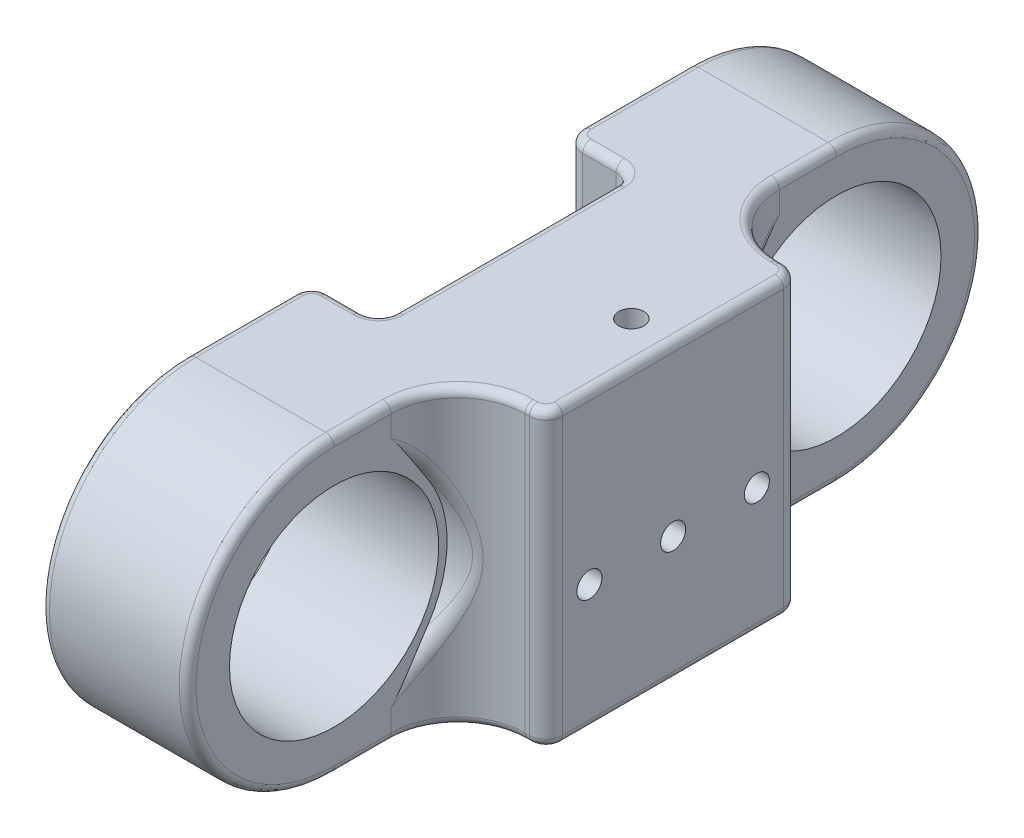
SolidWorks part; units mm, degrees
ref_plane "Front Plane" through (0, 0, 0) normal (0, 0, 1) x (1, 0, 0)
ref_plane "Top Plane" through (0, 0, 0) normal (0, 1, 0) x (1, 0, 0)
ref_plane "Right Plane" through (0, 0, 0) normal (1, 0, 0) x (0, 0, -1)
sketch "Sketch2" plane through (0, 0, 0) normal (0, 1, 0) x (1, 0, 0)
  line L0 (-11.1125, 19.29) -> (-0.9525, 19.29)
  line L1 (11.1125, -60.325) -> (-11.1125, -60.325)
  line L2 (11.1125, -60.325) -> (11.1125, 60.325)
  line L3 (11.1125, 60.325) -> (-11.1125, 60.325)
  line L4 (-11.1125, -60.325) -> (-11.1125, 60.325)
  line L5 (11.1125, -60.325) -> (-11.1125, 60.325) construction
  line L6 (11.1125, 60.325) -> (-11.1125, -60.325) construction
  line L7 (-0.9525, 19.29) -> (-0.9525, -19.29)
  line L8 (-0.9525, -19.29) -> (-11.1125, -19.29)
  line L9 (-11.1125, 18.02) -> (-0.9525, 18.02) construction
  line L10 (-182.965, -60.325) -> (-182.965, 60.325) construction
  line L12 (11.1125, 19.29) -> (24.4475, 19.29)
  line L13 (11.1125, 19.29) -> (11.1125, -19.29)
  line L14 (11.1125, -19.29) -> (24.4475, -19.29)
  line L15 (24.4475, 19.29) -> (24.4475, -19.29)
  line L16 (-0.9525, 18.02) -> (-0.9525, -18.02) construction
  line L17 (-0.9525, -18.02) -> (-11.1125, -18.02) construction
  line L18 (-11.1125, -18.02) -> (-0.9525, -18.02) construction
  line L19 (24.4475, 0) -> (-0.9525, 0) construction
  line L22 (-131.3125, 18.02) -> (-131.3125, -18.02) construction
  line L23 (-375.0525, 0) -> (31.3475, 0) construction
  circle A1 centre (18.0975, 0) radius 1.905
  point P0 (0, 0)
  point P9 (-0.9525, 0)
  point P21 (-6.0325, 18.02)
  point P22 (0, 0)
  dimension "D6" = 3.81
  dimension "D1" = 22.225
  dimension "D2" = 10.16
  dimension "D3" = 25.4
  dimension "D4" = 1.27
  dimension "D5" = 1.27
  dimension "D7" = 6.35
extrude "Boss-Extrude2" add sketch "Sketch2" along normal mid plane 44.45 contours L7 L8 L4 L1 L2 L3 L0 | L13 L12 L15 L14 | A1 region at (1.0328, 0, 0)
fillet "Fillet1" radius 10.16 2 edges at (11.1125, 0, 19.29) (11.1125, 0, -19.29)
sketch "Sketch3" plane through (11.1125, 0, 0) normal (1, 0, 0) x (0, 0, -1)
  line L0 (-60.325, 22.225) -> (-29.45, 22.225) construction
  line L1 (-60.325, -22.225) -> (-29.45, -22.225) construction
  line L2 (-60.325, 22.225) -> (-60.325, -22.225) construction
  line L3 (0, 19.558) -> (0, -19.558) construction
  line L4 (60.325, -22.225) -> (29.45, -22.225)
  line L5 (60.325, 22.225) -> (60.325, -22.225)
  line L6 (29.45, 22.225) -> (60.325, 22.225)
  line L7 (-29.45, -22.225) -> (-29.45, 22.225)
  line L8 (-29.45, 22.225) -> (-60.325, 22.225)
  line L9 (-60.325, 22.225) -> (-60.325, -22.225)
  line L10 (-60.325, -22.225) -> (-29.45, -22.225)
  line L12 (-29.45, 22.225) -> (-60.325, 22.225)
  line L13 (-60.325, 22.225) -> (-60.325, -22.225)
  line L14 (-60.325, -22.225) -> (-29.45, -22.225)
  line L15 (29.45, -22.225) -> (29.45, 22.225)
  line L20 (-29.45, -22.225) -> (-29.45, 22.225)
  circle A0 centre (-38.1, 0) radius 15.875
  circle A1 centre (-38.1, 0) radius 15.875 construction
  arc A2 (-38.1, 22.225) -> (-38.1, -22.225) centre (-38.1, 0) ccw
  arc A3 (38.1, 22.225) -> (38.1, -22.225) centre (38.1, 0) cw
  circle A4 centre (38.1, 0) radius 15.875
  circle A5 centre (-38.1, 0) radius 17.145
  circle A6 centre (38.1, 0) radius 17.145
  line M3 (-60.325, 22.225) -> (-60.325, -22.225)
  line M4 (-60.325, -22.225) -> (-29.45, -22.225)
  dimension "D1" = 0
  dimension "D2" = 34.29
extrude "Cut-Extrude1" cut sketch "Sketch3" against normal up to surface and the other way up to surface contours A0 | A2 L12 M3 | A2 L13 M4 | A4 | L6 A3 L5 | L5 A3 L4 | A0 | A4 region at (11.1125, -17.2606, -55.3606) region at (11.1125, 17.2606, -55.3606) region at (11.1125, 0, -40.4962) region at (11.1125, -17.2606, 55.3606) region at (11.1125, 0, 40.4962) region at (11.1125, 17.2606, 55.3606) up to face at (-11.1125, 0, 39.8075) other way up to face at (24.4475, 0, 0)
extrude "Cut-Extrude2" cut sketch "Sketch3<3>" along normal up to surface (13.335 mm away) contours A6 | A5 up to face at (24.4475, 0, 0)
sketch "Sketch3<3>" plane through (11.1125, 0, 0) normal (1, 0, 0) x (0, 0, -1) same geometry as "Sketch3"
fillet "Fillet2" radius 2.54 2 edges at (15.6715, 0.7919, 20.9733) (15.6715, 0.7919, -20.9733)
fillet "Fillet3" radius 2.54 6 edges at (-0.9525, 0, -19.29) (-0.9525, 0, 19.29) (-11.1125, 0, 19.29) (-11.1125, 0, -19.29) (24.4475, 0, 19.29) (24.4475, 0, -19.29)
fillet "Fillet4" radius 1.27 38 edges at (-11.1125, 22.225, 29.965) (-10.3686, 22.225, 20.0339) (-6.0325, 22.225, 19.29) (-1.6964, 22.225, 18.5461) (-0.9525, 22.225, 0) (-1.6964, 22.225, -18.5461) (-6.0325, 22.225, -19.29) (-10.3686, 22.225, -20.0339) (-11.1125, 22.225, -29.965) (-11.1125, 0, -60.325) (-11.1125, -22.225, -29.965) (-10.3686, -22.225, -20.0339) (-6.0325, -22.225, -19.29) (-1.6964, -22.225, -18.5461) (-0.9525, -22.225, 0) (-1.6964, -22.225, 18.5461) (-6.0325, -22.225, 19.29) (-10.3686, -22.225, 20.0339) (-11.1125, -22.225, 29.965) (11.1125, -22.225, -33.775) (14.0883, -22.225, 22.2658) (24.4475, -22.225, 0) (14.0883, -22.225, -22.2658) (11.1125, 0, -60.325) (11.1125, 22.225, -33.775) (14.0883, 22.225, -22.2658) (24.4475, 22.225, 0) (14.0883, 22.225, 22.2658) (-11.1125, 0, 60.325) (11.1125, 0, 60.325) (21.59, -22.225, 19.29) (21.59, 22.225, 19.29) (23.7036, -22.225, 18.5461) (23.7036, -22.225, -18.5461) (21.59, -22.225, -19.29) (21.59, 22.225, -19.29) (23.7036, 22.225, -18.5461) (23.7036, 22.225, 18.5461)
sketch "Sketch4" plane through (0, -22.225, 0) normal (0, -1, 0) x (1, 0, 0)
  line L0 (24.4475, 19.29) -> (24.4475, -19.29) construction
  line L1 (3.81, 15.875) -> (13.335, 15.875) construction
  line L2 (3.81, 15.875) -> (3.81, 9.525) construction
  line L3 (3.81, 9.525) -> (13.335, 9.525) construction
  line L4 (13.335, 15.875) -> (13.335, 9.525) construction
  line L5 (3.81, 3.175) -> (13.335, 3.175) construction
  line L6 (3.81, 3.175) -> (3.81, -3.175) construction
  line L7 (3.81, -3.175) -> (13.335, -3.175) construction
  line L8 (13.335, 3.175) -> (13.335, -3.175) construction
  line L9 (3.81, -9.525) -> (13.335, -9.525) construction
  line L10 (3.81, -9.525) -> (3.81, -15.875) construction
  line L11 (3.81, -15.875) -> (13.335, -15.875) construction
  line L12 (13.335, -9.525) -> (13.335, -15.875) construction
  line L13 (24.4475, 0) -> (-0.9525, 0) construction
  line L14 (-0.9525, -16.75) -> (-0.9525, 16.75) construction
  line L15 (3.556, 16.129) -> (13.589, 16.129)
  line L16 (13.589, 16.129) -> (13.589, 9.271)
  line L17 (3.556, 9.271) -> (13.589, 9.271)
  line L18 (3.556, 16.129) -> (3.556, 9.271)
  line L19 (3.556, 3.429) -> (13.589, 3.429)
  line L20 (13.589, 3.429) -> (13.589, -3.429)
  line L21 (3.556, -3.429) -> (13.589, -3.429)
  line L22 (3.556, 3.429) -> (3.556, -3.429)
  line L23 (3.556, -9.271) -> (13.589, -9.271)
  line L24 (13.589, -9.271) -> (13.589, -16.129)
  line L25 (3.556, -16.129) -> (13.589, -16.129)
  line L26 (3.556, -9.271) -> (3.556, -16.129)
  point P12 (24.4475, 0)
  point P13 (13.335, 0)
  point P21 (8.5725, 15.875)
  dimension "D1" = 6.35
  dimension "D2" = 15.875
  dimension "D3" = 15.875
  dimension "D4" = 9.525
  dimension "D5" = 4.7625
  dimension "D6" = 0.254
extrude "Cut-Extrude3" cut sketch "Sketch4" against normal blind 25.4
sketch "Sketch5" plane through (-0.9525, 0, 0) normal (-1, 0, 0) x (0, 0, 1)
  line L0 (9.271, -22.225) -> (16.129, -22.225) construction
  line L1 (16.129, -22.225) -> (16.129, 3.175) construction
  line L2 (16.129, 3.175) -> (9.271, 3.175) construction
  line L3 (9.271, 3.175) -> (9.271, -22.225) construction
  line L4 (-3.429, -22.225) -> (3.429, -22.225) construction
  line L5 (3.429, -22.225) -> (3.429, 3.175) construction
  line L6 (3.429, 3.175) -> (-3.429, 3.175) construction
  line L7 (-3.429, 3.175) -> (-3.429, -22.225) construction
  line L8 (-16.129, -22.225) -> (-9.271, -22.225) construction
  line L9 (-9.271, -22.225) -> (-9.271, 3.175) construction
  line L10 (-9.271, 3.175) -> (-16.129, 3.175) construction
  line L11 (-16.129, 3.175) -> (-16.129, -22.225) construction
  line L12 (9.271, -22.225) -> (16.129, -22.225) construction
  line L13 (16.129, -22.225) -> (16.129, 3.175) construction
  line L14 (16.129, 3.175) -> (9.271, 3.175) construction
  line L15 (9.271, 3.175) -> (9.271, -22.225) construction
  line L16 (-3.429, -22.225) -> (3.429, -22.225) construction
  line L17 (3.429, -22.225) -> (3.429, 3.175) construction
  line L18 (3.429, 3.175) -> (-3.429, 3.175) construction
  line L19 (-3.429, 3.175) -> (-3.429, -22.225) construction
  line L20 (-16.129, -22.225) -> (-9.271, -22.225) construction
  line L21 (-9.271, -22.225) -> (-9.271, 3.175) construction
  line L22 (-9.271, 3.175) -> (-16.129, 3.175) construction
  line L23 (-16.129, 3.175) -> (-16.129, -22.225) construction
  line L24 (-16.129, -3.175) -> (-9.271, -3.175) construction
  line L25 (9.271, -3.175) -> (16.129, -3.175) construction
  circle A0 centre (-12.7, -3.175) radius 1.905
  circle A1 centre (0, -3.175) radius 1.905
  circle A2 centre (12.7, -3.175) radius 1.905
  point P14 (0, 0)
  dimension "D1" = 3.81
  dimension "D2" = 6.35
  dimension "D3" = 3
extrude "Cut-Extrude4" cut sketch "Sketch5" against normal up to surface (25.4 mm away) up to face at (24.4475, 0, 0)
ref_plane "Plane1" through (8.5725, 0, 0) normal (-1, 0, 0) x (0, 0, 1)
